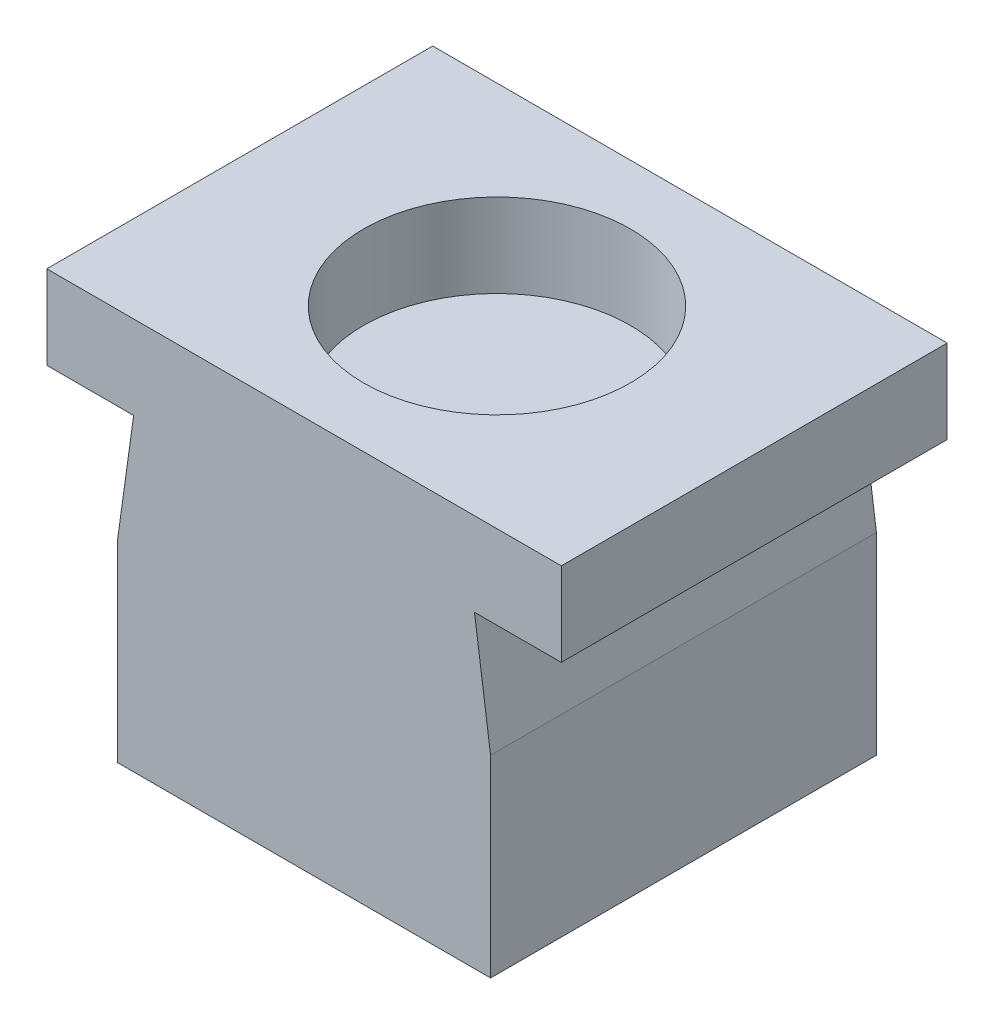
SolidWorks part; units mm, degrees
ref_plane "Front Plane" through (0, 0, 0) normal (0, 0, 1) x (1, 0, 0)
ref_plane "Top Plane" through (0, 0, 0) normal (0, 1, 0) x (1, 0, 0)
ref_plane "Right Plane" through (0, 0, 0) normal (1, 0, 0) x (0, 0, -1)
sketch "Sketch1" plane through (0, 0, 0) normal (0, 0, 1) x (1, 0, 0)
  line L0 (-20, 6.5) -> (-20, 0)
  line L1 (-20, 0) -> (-13.25, 0)
  line L2 (-13.25, 0) -> (-14.5, -9)
  line L3 (-14.5, -9) -> (-14.5, -24)
  line L4 (-14.5, -24) -> (14.5, -24)
  line L5 (0, -24) -> (0, 6.5) construction
  line L6 (20, 6.5) -> (-20, 6.5)
  line L7 (-13.25, 0) -> (13.25, 0) construction
  line L8 (14.5, -9) -> (14.5, -24)
  line L9 (13.25, 0) -> (14.5, -9)
  line L10 (20, 0) -> (13.25, 0)
  line L11 (20, 6.5) -> (20, 0)
  point P10 (0, 0)
  dimension "D1" = 20
  dimension "D2" = 14.5
  dimension "D3" = 13.25
  dimension "D4" = 9
  dimension "D5" = 6.5
  dimension "D6" = 24
extrude "Boss-Extrude1" add sketch "Sketch1" along normal blind 15 and the other way blind 15
sketch "Sketch2" plane through (0, 6.5, 0) normal (0, 1, 0) x (1, 0, 0)
  circle A0 centre (0, 0) radius 10.375
  dimension "D1" = 20.75
extrude "Cut-Extrude1" cut sketch "Sketch2" against normal blind 6.5
